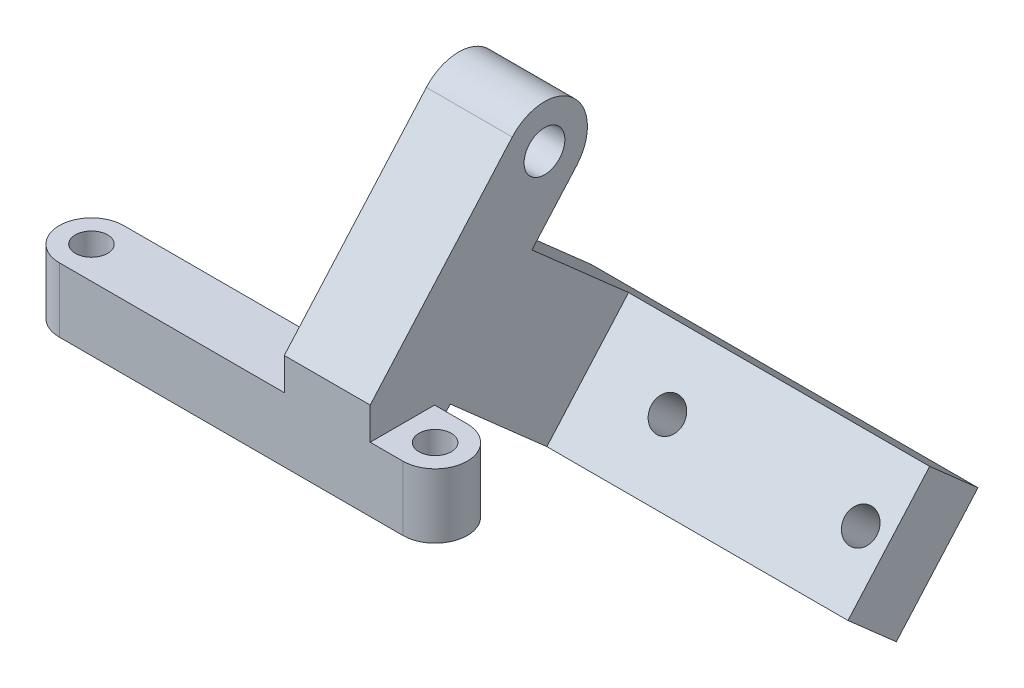
SolidWorks part; units mm, degrees
ref_plane "前基準面" through (0, 0, 0) normal (0, 0, 1) x (1, 0, 0)
ref_plane "上基準面" through (0, 0, 0) normal (0, 1, 0) x (1, 0, 0)
ref_plane "右基準面" through (0, 0, 0) normal (1, 0, 0) x (0, 0, -1)
sketch "草圖1" plane through (0, 0, 0) normal (0, 1, 0) x (1, 0, 0)
  line L0 (-38.677, 0) -> (-6.677, 0) construction
  line L1 (-38.677, 3) -> (-6.677, 3)
  line L2 (-38.677, -3) -> (-6.677, -3)
  line L4 (-17.7228, 3) -> (-9.7228, 3)
  line L5 (-17.7228, 3) -> (-17.7228, -3)
  line L6 (-17.7228, -3) -> (-9.7228, -3)
  line L7 (-9.7228, 3) -> (-9.7228, -3)
  arc A0 (-38.677, 3) -> (-38.677, -3) centre (-38.677, 0) ccw
  arc A1 (-6.677, -3) -> (-6.677, 3) centre (-6.677, 0) ccw
  circle A2 centre (-6.677, 0) radius 1.5
  circle A3 centre (-38.677, 0) radius 1.5
  point P3 (-22.677, 0)
  dimension "D1" = 32
  dimension "D2" = 8
  dimension "D4" = 3
  dimension "D3" = 6
extrude "填料-伸長2" add sketch "草圖1" against normal blind 6 contours A3 L5 L1 A0 L2 | L5 L0 L7 L1 | L0 L5 L2 L7 | L2 A1 L1 L7 A2 region at (-17.9697, 0, 1.5) region at (-13.7228, 0, -1.5) region at (-13.7228, 0, 1.5) region at (-9.6376, 0, -1.5)
extrude "填料-伸長3" add sketch "草圖1<4>" along normal blind 3 contours L0 L5 L2 L7 | L5 L0 L7 L1 region at (-13.7228, 0, -1.5) region at (-13.7228, 0, 1.5)
sketch "草圖1<4>" plane through (0, 0, 0) normal (0, 1, 0) x (1, 0, 0) same geometry as "草圖1"
sketch "草圖3" plane through (-9.7228, 0, 0) normal (1, 0, 0) x (0, 0, -1)
  line L0 (-3, 3) -> (-3, 0) construction
  line L2 (-3, 2.6558) -> (-3, 0)
  line L3 (13.2288, 15.3542) -> (0, 0.3542) construction
  line L4 (3, -6) -> (3, 0) construction
  line L5 (16.2288, 12.7085) -> (10.2288, 18)
  line L6 (16.2288, 12.7085) -> (3, -2.2915)
  line L7 (10.2288, 18) -> (-3, 3)
  line L8 (3, -2.2915) -> (-3, 3)
  line L9 (16.2288, 12.7085) -> (3, -2.2915)
  line L10 (10.2288, 18) -> (-3, 3)
  arc A0 (16.2288, 12.7085) -> (10.2288, 18) centre (13.2288, 15.3542) ccw
  arc A1 (-3, 3) -> (3, -2.2915) centre (0, 0.3542) ccw
  point P15 (6.6144, 7.8542)
  dimension "D1" = 8
  dimension "D2" = 20
extrude "填料-伸長28" add sketch "草圖3" against normal blind 8 contours L5 A0 | L5 L7 L8 L6 region at (-9.7228, 16.6275, -14.3516)
sketch "草圖4" plane through (0, -2.4908, -2.8243) normal (0, -0.6614, -0.75) x (-1, 0, 0)
  line L0 (9.7228, 13.9612) -> (9.7228, 2.4612)
  line L1 (9.7228, 13.9612) -> (17.6833, 13.9612)
  line L2 (9.7228, 2.4612) -> (17.6833, 2.4612)
  line L3 (17.6833, 13.9612) -> (17.6833, 2.4612)
  dimension "D1" = 11.5
extrude "填料-伸長29" add sketch "草圖4" along normal blind 18
sketch "草圖6" plane through (-17.6833, 0, 0) normal (-1, 0, 0) x (0, 0, 1)
  line L0 (-25.5587, -3.9258) -> (-17.9522, -12.5508)
  line L1 (-25.5587, -3.9258) -> (-21.0587, 0.0429)
  line L2 (-17.9522, -12.5508) -> (-13.4522, -8.5821)
  line L3 (-21.0587, 0.0429) -> (-13.4522, -8.5821)
  line L4 (-17.9522, -12.5508) -> (-25.5587, -3.9258) construction
  line L5 (-25.5587, -3.9258) -> (-12.0587, 7.9801) construction
  dimension "D1" = 6
extrude "填料-伸長30" add sketch "草圖6" against normal blind 36 contours L0 L1 L3 L2
sketch "草圖7" plane through (0, -14.3966, -16.3243) normal (0, -0.6614, -0.75) x (-1, 0, 0)
  line L0 (-18.3167, 2.4612) -> (-18.3167, 5.5409)
  line L1 (63.8434, 13.9612) -> (-18.3167, 13.9612)
  line L2 (-18.3167, 13.9612) -> (17.6833, 13.9612) construction
  line L3 (-18.3167, 13.9612) -> (-18.3167, 10.8815)
  line L4 (-18.3167, 13.9612) -> (-18.3167, 2.4612) construction
  line L5 (-18.3167, 8.2112) -> (55.4337, 8.2112) construction
  line L6 (63.8434, 2.4612) -> (-18.3167, 2.4612)
  circle A0 centre (2.3448, 8.278) radius 1.5
  circle A1 centre (-15.6552, 8.278) radius 1.5
  arc A2 (-18.3167, 10.8815) -> (63.8434, 13.9612) centre (22.7634, 12.4213) ccw
  arc A3 (-18.3167, 5.5409) -> (63.8434, 2.4612) centre (22.7634, 4.001) cw
  dimension "D1" = 3
  dimension "D2" = 3
  dimension "D3" = 18
sketch "草圖8" plane through (-9.7228, 0, 0) normal (1, 0, 0) x (0, 0, -1)
  circle A0 centre (13.2288, 15.3542) radius 1.9
  dimension "D1" = 3.8
extrude "除料-伸長2" cut sketch "草圖8" against normal blind 19 contours A0
extrude "除料-伸長3" cut sketch "草圖7" against normal blind 10 contours A1 | A0
